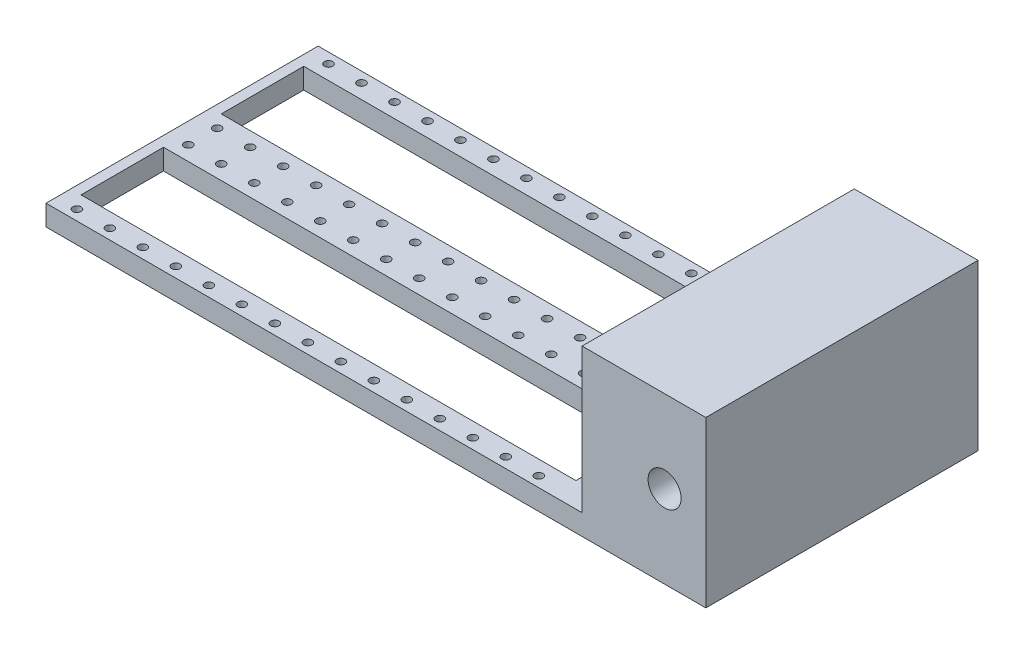
SolidWorks part; units mm, degrees
ref_plane "Front Plane" through (0, 0, 0) normal (0, 0, 1) x (1, 0, 0)
ref_plane "Top Plane" through (0, 0, 0) normal (0, 1, 0) x (1, 0, 0)
ref_plane "Right Plane" through (0, 0, 0) normal (1, 0, 0) x (0, 0, -1)
sketch "Sketch1" plane through (0, 0, 0) normal (0, 1, 0) x (1, 0, 0)
  line L1 (-80, 33) -> (80, 33)
  line L2 (-80, 33) -> (-80, -33)
  line L3 (-80, -33) -> (80, -33)
  line L4 (80, 33) -> (80, -33)
  line L5 (-80, 33) -> (80, -33) construction
  line L6 (-80, -33) -> (80, 33) construction
  point P0 (0, 0)
  dimension "D1" = 160
  dimension "D2" = 66
extrude "Boss-Extrude1" add sketch "Sketch1" along normal blind 40
sketch "Sketch2" plane through (0, 0, 33) normal (0, 0, 1) x (1, 0, 0)
  line L0 (80, 40) -> (80, 0) construction
  line L1 (-80, 40) -> (80, 40) construction
  line L2 (-80, 40) -> (50, 40)
  line L3 (-80, 40) -> (-80, 5)
  line L4 (-80, 5) -> (50, 5)
  line L5 (50, 40) -> (50, 5)
  line L6 (-80, 40) -> (50, 5) construction
  line L7 (-80, 5) -> (50, 40) construction
  line L8 (-80, 40) -> (-80, 0) construction
  circle A0 centre (70, 20) radius 4
  point P4 (80, 20)
  point P5 (-15, 22.5)
  point P15 (0, 0)
  point P21 (11.78, 15)
  dimension "D1" = 8
  dimension "D2" = 10
  dimension "D3" = 35
  dimension "D4" = 130
extrude "Cut-Extrude1" cut sketch "Sketch2" against normal through all
sketch "Sketch3" plane through (0, 40, 0) normal (0, 1, 0) x (1, 0, 0)
  line L0 (-80, 33) -> (-80, -33) construction
  line L1 (80, 33) -> (50, 33) construction
  line L2 (-75, 30.5) -> (-67, 30.5) construction
  line L3 (-75, 3.5) -> (-67, 3.5) construction
  line L4 (0, 0) -> (13.7346, 0) construction
  line L5 (-80, 33) -> (-80, -33) construction
  line L6 (-75, -30.5) -> (-75, -3.5) construction
  line L7 (-75, 30.5) -> (-75, 3.5) construction
  line L8 (-77.5, 27) -> (42.5, 27)
  line L9 (-77.5, 27) -> (-77.5, 7)
  line L10 (-77.5, 7) -> (42.5, 7)
  line L11 (42.5, 27) -> (42.5, 7)
  line L12 (-75, -3.5) -> (-67, -3.5) construction
  line L13 (-75, -30.5) -> (-67, -30.5) construction
  line L14 (42.5, -27) -> (42.5, -7)
  line L15 (-77.5, -7) -> (42.5, -7)
  line L16 (-77.5, -27) -> (-77.5, -7)
  line L17 (-77.5, -27) -> (42.5, -27)
  circle A0 centre (-75, 30.5) radius 1
  circle A1 centre (-75, 3.5) radius 1
  circle A2 centre (-67, 30.5) radius 1
  circle A3 centre (-59, 30.5) radius 1
  circle A4 centre (-51, 30.5) radius 1
  circle A5 centre (-43, 30.5) radius 1
  circle A6 centre (-35, 30.5) radius 1
  circle A7 centre (-27, 30.5) radius 1
  circle A8 centre (-19, 30.5) radius 1
  circle A9 centre (-11, 30.5) radius 1
  circle A10 centre (-3, 30.5) radius 1
  circle A11 centre (-67, 3.5) radius 1
  circle A12 centre (-59, 3.5) radius 1
  circle A13 centre (-51, 3.5) radius 1
  circle A14 centre (-43, 3.5) radius 1
  circle A15 centre (-35, 3.5) radius 1
  circle A16 centre (-27, 3.5) radius 1
  circle A17 centre (-19, 3.5) radius 1
  circle A18 centre (-11, 3.5) radius 1
  circle A19 centre (-3, 3.5) radius 1
  circle A40 centre (5, 30.5) radius 1
  circle A41 centre (13, 30.5) radius 1
  circle A42 centre (21, 30.5) radius 1
  circle A43 centre (29, 30.5) radius 1
  circle A44 centre (37, 30.5) radius 1
  circle A45 centre (5, 3.5) radius 1
  circle A46 centre (13, 3.5) radius 1
  circle A47 centre (21, 3.5) radius 1
  circle A48 centre (29, 3.5) radius 1
  circle A49 centre (37, 3.5) radius 1
  circle A50 centre (37, -3.5) radius 1
  circle A51 centre (29, -3.5) radius 1
  circle A52 centre (21, -3.5) radius 1
  circle A53 centre (13, -3.5) radius 1
  circle A54 centre (5, -3.5) radius 1
  circle A55 centre (37, -30.5) radius 1
  circle A56 centre (29, -30.5) radius 1
  circle A57 centre (21, -30.5) radius 1
  circle A58 centre (13, -30.5) radius 1
  circle A59 centre (5, -30.5) radius 1
  circle A60 centre (-3, -3.5) radius 1
  circle A61 centre (-11, -3.5) radius 1
  circle A62 centre (-19, -3.5) radius 1
  circle A63 centre (-27, -3.5) radius 1
  circle A64 centre (-35, -3.5) radius 1
  circle A65 centre (-43, -3.5) radius 1
  circle A66 centre (-51, -3.5) radius 1
  circle A67 centre (-59, -3.5) radius 1
  circle A68 centre (-67, -3.5) radius 1
  circle A69 centre (-3, -30.5) radius 1
  circle A70 centre (-11, -30.5) radius 1
  circle A71 centre (-19, -30.5) radius 1
  circle A72 centre (-27, -30.5) radius 1
  circle A73 centre (-35, -30.5) radius 1
  circle A74 centre (-43, -30.5) radius 1
  circle A75 centre (-51, -30.5) radius 1
  circle A76 centre (-59, -30.5) radius 1
  circle A77 centre (-67, -30.5) radius 1
  circle A78 centre (-75, -3.5) radius 1
  circle A79 centre (-75, -30.5) radius 1
  point P96 (-77.5, 17)
  point P97 (-75, 17)
  dimension "D1" = 2
  dimension "D3" = 2.5
  dimension "D4" = 27
  dimension "D2" = 5
  dimension "D6" = 8
  dimension "D8" = 8
  dimension "D9" = 20
  dimension "D10" = 120
  dimension "D11" = 2.5
  dimension "D5" = 15
  dimension "D7" = 15
extrude "Cut-Extrude2" cut sketch "Sketch3" against normal through all
